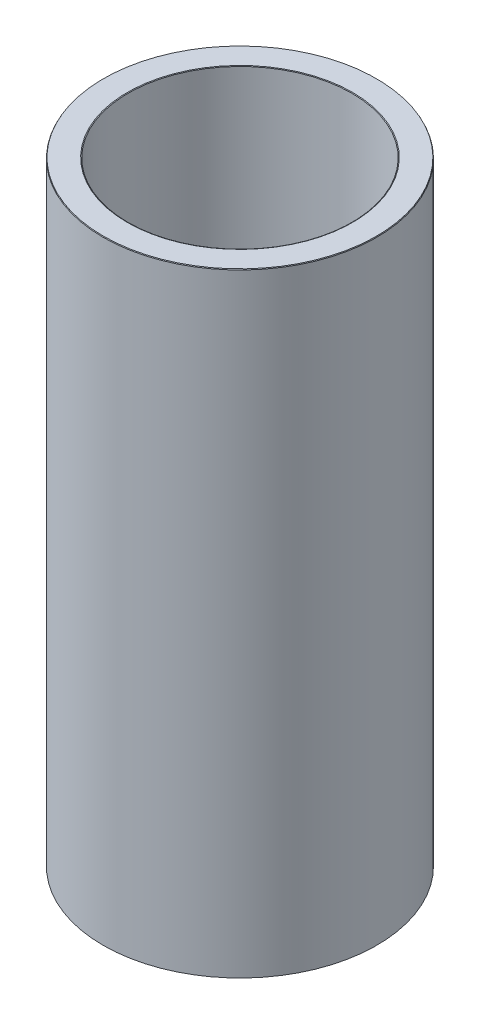
SolidWorks part; units mm, degrees
ref_plane "Front Plane" through (0, 0, 0) normal (0, 0, 1) x (1, 0, 0)
ref_plane "Top Plane" through (0, 0, 0) normal (0, 1, 0) x (1, 0, 0)
ref_plane "Right Plane" through (0, 0, 0) normal (1, 0, 0) x (0, 0, -1)
sketch "Sketch1" plane through (0, 0, 0) normal (0, 1, 0) x (1, 0, 0)
  circle A0 centre (0, 0) radius 52.5
  dimension "SLEEVE_OD" = 105
extrude "Boss-Extrude1" add sketch "Sketch1" along normal blind 235.6767
sketch "Sketch2" plane through (0, 0, 0) normal (0, 1, 0) x (1, 0, 0)
  circle A0 centre (0, 0) radius 42.9294
  dimension "BORE_D" = 85.8589
extrude "Cut-Extrude1" cut sketch "Sketch2" along normal through all
chamfer "Chamfer1" distance 0.2916 angle 26.697 4 edges at (0, 235.6767, 42.9294) (0, 0, 42.9294) (0, 0, 52.5) (0, 235.6767, 52.5) first distance on face at (0, 235.6767, 42.9294) first distance on face at (0, 0, 42.9294) first distance on face at (0, 235.6767, 52.5)
